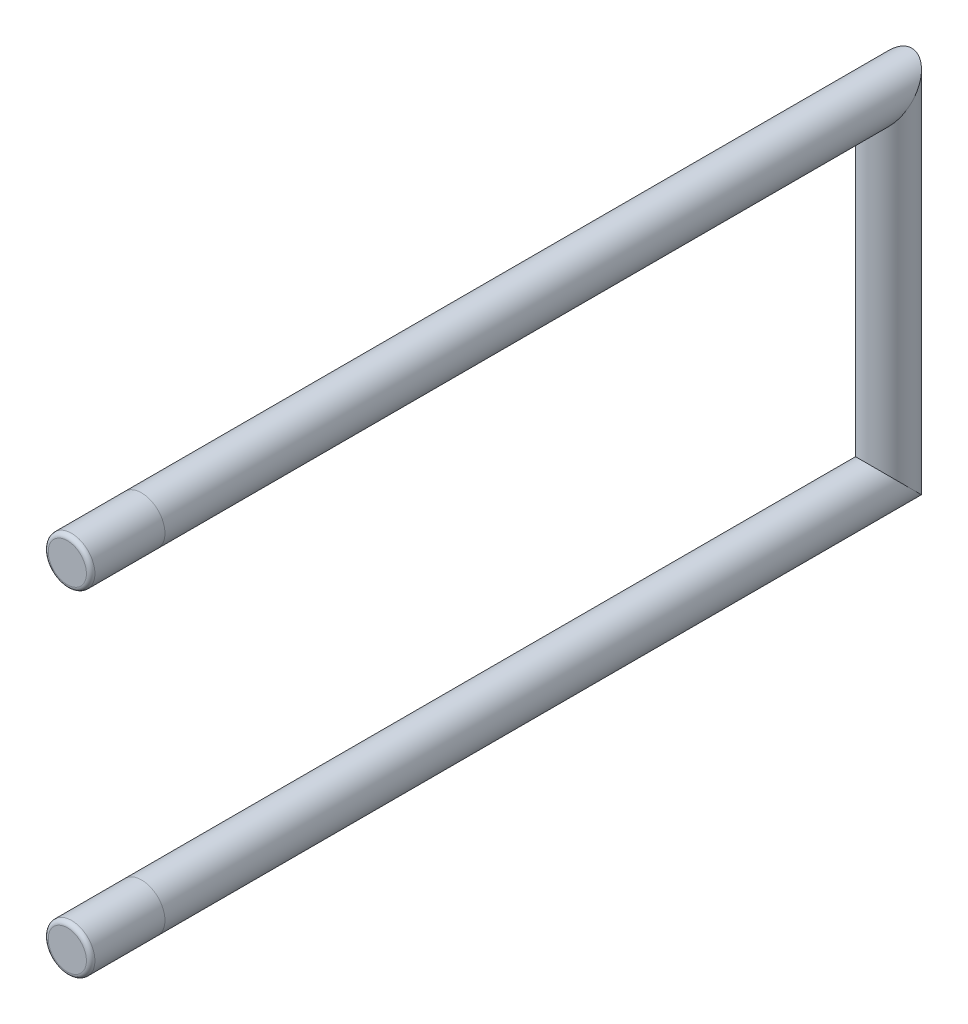
SolidWorks part; units mm, degrees
ref_plane "前视基准面" through (0, 0, 0) normal (0, 0, 1) x (1, 0, 0)
ref_plane "上视基准面" through (0, 0, 0) normal (0, 1, 0) x (1, 0, 0)
ref_plane "右视基准面" through (0, 0, 0) normal (1, 0, 0) x (0, 0, -1)
sketch "草图1" plane through (0, 0, 0) normal (0, 0, 1) x (1, 0, 0)
  circle A0 centre (0, 0) radius 11
  dimension "D1" = 22
extrude "拉伸1" add sketch "草图1" along normal blind 352
sketch "草图2" plane through (0, 0, 0) normal (0, 1, 0) x (1, 0, 0)
  circle A0 centre (0, 0) radius 11
  dimension "D1" = 22
extrude "拉伸2" add sketch "草图2" along normal blind 158
ref_axis "基准轴1" through (0, 178.2869, 0) along (0, -1, 0)
pattern_linear "阵列(线性)1" count 2 spacing 158 along (0, 1, 0) of "拉伸1"
sketch "草图3" plane through (0, 0, 352) normal (0, 0, 1) x (1, 0, 0)
  circle A0 centre (0, 158) radius 10.9995
  circle A1 centre (0, 0) radius 10.9995
  circle A2 centre (0, 158) radius 11 construction
  dimension "D1" = 21.999
extrude "拉伸3" add sketch "草图3" along normal blind 35
chamfer "倒角1" distance 21.999 angle 45 2 edges at (0, 0, 0) (0, 158, 0)
fillet "圆角1" radius 2 2 edges at (10.9995, 0, 387) (10.9995, 158, 387)
